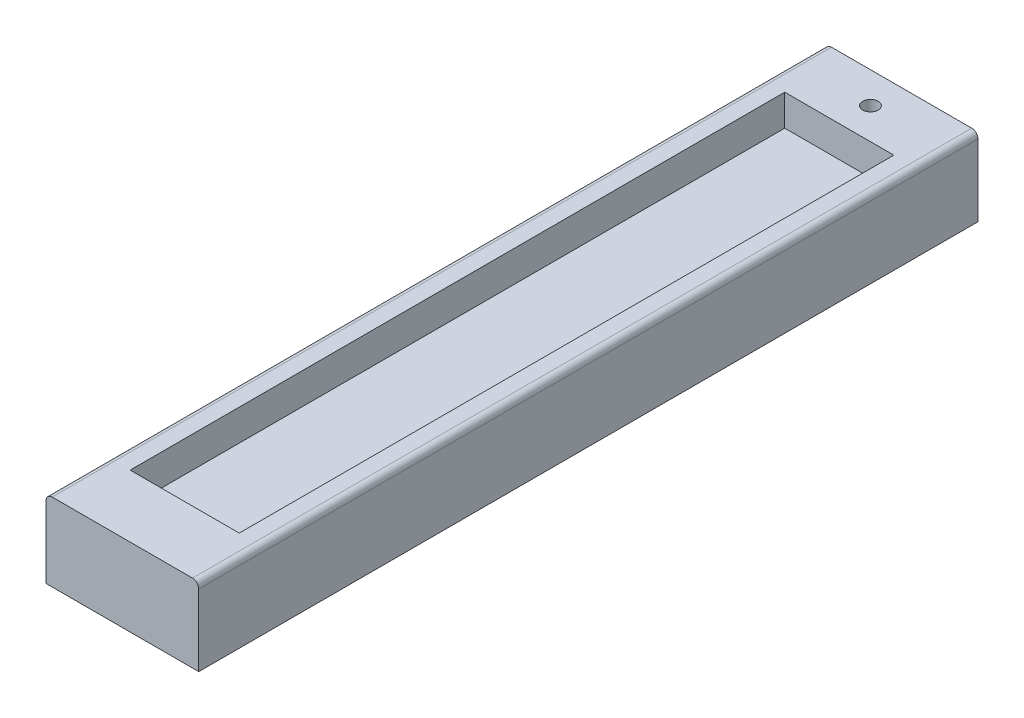
SolidWorks part; units mm, degrees
ref_plane "Front Plane" through (0, 0, 0) normal (0, 0, 1) x (1, 0, 0)
ref_plane "Top Plane" through (0, 0, 0) normal (0, 1, 0) x (1, 0, 0)
ref_plane "Right Plane" through (0, 0, 0) normal (1, 0, 0) x (0, 0, -1)
sketch "Sketch1" plane through (0, 0, 0) normal (0, 0, 1) x (1, 0, 0)
  line L1 (24.5, -10) -> (-24.5, -10)
  line L2 (24.5, -10) -> (24.5, 10)
  line L3 (24.5, 10) -> (-24.5, 10)
  line L4 (-24.5, -10) -> (-24.5, 10)
  line L5 (0, 10) -> (0, -10) construction
  line L6 (24.5, 0) -> (-24.5, 0) construction
  point P0 (0, 0)
  dimension "D1" = 20
  dimension "D2" = 49
extrude "Boss-Extrude1" add sketch "Sketch1" along normal mid plane 250
sketch "Sketch3" plane through (0, 10, 0) normal (0, 1, 0) x (1, 0, 0)
  line L0 (24.5, 125) -> (-24.5, 125) construction
  line L1 (24.5, 125) -> (-24.5, 125)
  line L2 (24.5, 125) -> (24.5, -125)
  line L3 (24.5, -125) -> (-24.5, -125)
  line L4 (-24.5, 125) -> (-24.5, -125)
  line L5 (0, -125) -> (0, 125) construction
  line L6 (24.5, 0) -> (-24.5, 0) construction
  point P0 (0, 0)
  dimension "D1" = 49
extrude "Boss-Extrude2" add sketch "Sketch3" along normal blind 5
ref_plane "Plane1" through (0, 15, 0) normal (0, 1, 0) x (1, 0, 0)
sketch "Sketch2" plane through (0, 15, 0) normal (0, 1, 0) x (1, 0, 0)
  line L1 (24.5, 125) -> (-24.5, 125) construction
  circle A0 centre (0, 115) radius 2.46
  dimension "D1" = 4.92
  dimension "D2" = 10
extrude "Cut-Extrude1" cut sketch "Sketch2" against normal blind 10 and the other way through all
sketch "Sketch5" plane through (0, 15, 0) normal (0, 1, 0) x (1, 0, 0)
  line L1 (-17.5, -105) -> (17.5, -105)
  line L2 (-17.5, -105) -> (-17.5, 105)
  line L3 (-17.5, 105) -> (17.5, 105)
  line L4 (17.5, -105) -> (17.5, 105)
  line L5 (-17.5, -105) -> (17.5, 105) construction
  line L6 (-17.5, 105) -> (17.5, -105) construction
  point P0 (0, 0)
  dimension "D1" = 35
  dimension "D2" = 210
extrude "Cut-Extrude3" cut sketch "Sketch5" against normal blind 10
fillet "Fillet1" radius 2 2 edges at (-24.5, 15, 0) (24.5, 15, 0)
sketch "Sketch4" plane through (0, -10, 0) normal (0, -1, 0) x (1, 0, 0)
  line L0 (-24.5, 125) -> (24.5, 125) construction
  line L5 (24.5, 125) -> (24.5, -125) construction
  circle A0 centre (-0.5, 110) radius 7.874
  dimension "D2" = 15.748
  dimension "D1" = 15
  dimension "D3" = 25
extrude "Cut-Extrude2" cut sketch "Sketch4" against normal blind 10
